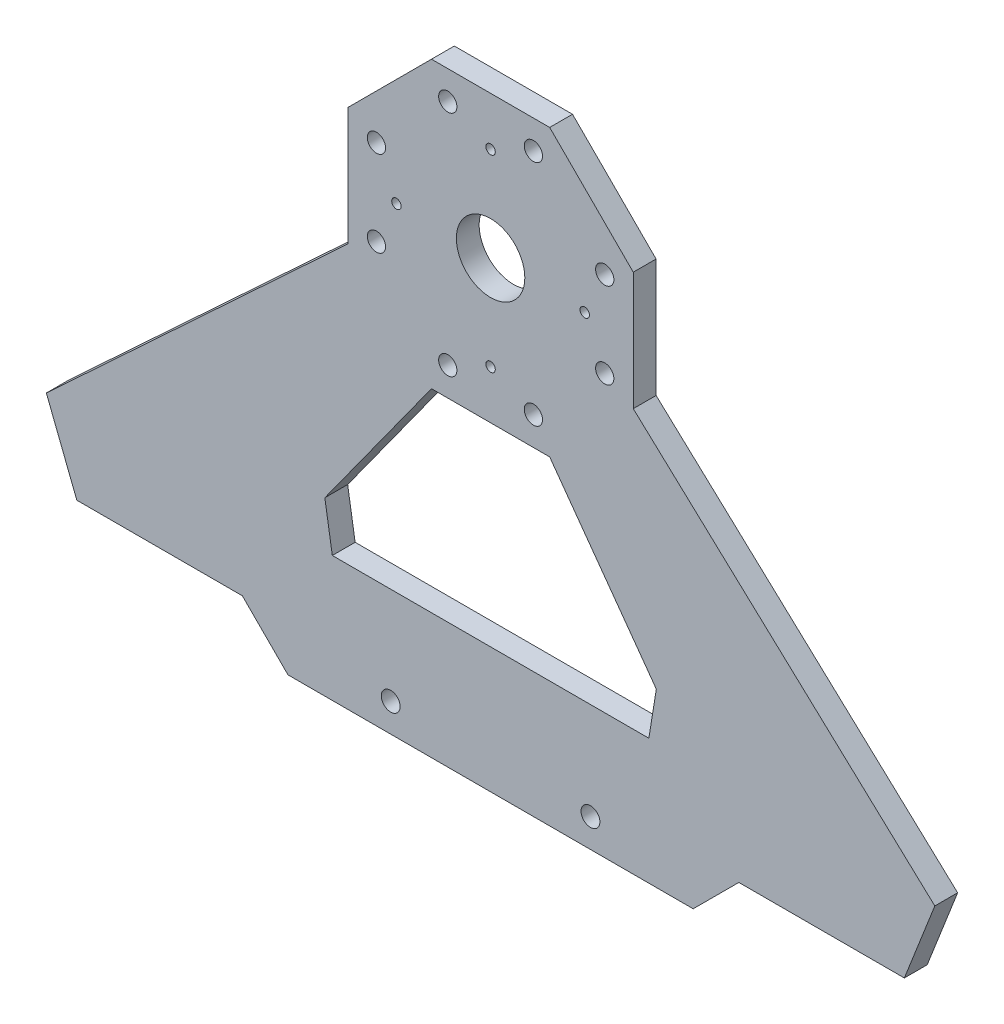
SolidWorks part; units mm, degrees
ref_plane "前视基准面" through (0, 0, 0) normal (0, 0, 1) x (1, 0, 0)
ref_plane "上视基准面" through (0, 0, 0) normal (0, 1, 0) x (1, 0, 0)
ref_plane "右视基准面" through (0, 0, 0) normal (1, 0, 0) x (0, 0, -1)
sketch "草图2" plane through (0, 0, 0) normal (0, 0, 1) x (1, 0, 0)
  line L1 (10.3553, 25) -> (-10.3553, 25)
  line L2 (-10.3553, 25) -> (-25, 10.3553)
  line L3 (-25, 10.3553) -> (-25, -10.3553)
  line L4 (-25, -10.3553) -> (-10.3553, -25)
  line L5 (-10.3553, -25) -> (10.3553, -25)
  line L6 (10.3553, -25) -> (25, -10.3553)
  line L7 (25, -10.3553) -> (25, 10.3553)
  line L8 (25, 10.3553) -> (10.3553, 25)
  circle A0 centre (0, 0) radius 25 construction
  circle A1 centre (-16.5, 0) radius 0.825
  circle A2 centre (0, 16.5) radius 0.825
  circle A3 centre (16.5, 0) radius 0.825
  circle A4 centre (0, -16.5) radius 0.825
  circle A5 centre (0, 0) radius 6
  point P22 (0, 0)
  dimension "D2" = 4
  dimension "D3" = 1.65
  dimension "D4" = 33
  dimension "D5" = 12
  dimension "D1" = 50
extrude "凸台-拉伸1" add sketch "草图2" along normal mid plane 4
sketch "草图4" plane through (0, 0, -2) normal (0, 0, -1) x (-1, 0, 0)
  line L0 (0, 2.2) -> (0, -2.2) construction
  line L1 (10.3553, -25) -> (-10.3553, -25) construction
  circle A0 centre (-7.5, -20) radius 1.6
  circle A1 centre (7.5, -20) radius 1.6
  circle A4 centre (-20, 7.5) radius 1.6
  circle A5 centre (-20, -7.5) radius 1.6
  circle A6 centre (7.5, 20) radius 1.6
  circle A7 centre (-7.5, 20) radius 1.6
  circle A8 centre (20, -7.5) radius 1.6
  circle A9 centre (20, 7.5) radius 1.6
  point P23 (0, 0)
  dimension "D1" = 15
  dimension "D2" = 5
  dimension "D3" = 3.2
  dimension "D4" = 4
extrude "切除-拉伸1" cut sketch "草图4" against normal blind 15
sketch "草图5" plane through (0, 0, 0) normal (0, 0, 1) x (1, 0, 0)
  line L0 (-25, -10.3553) -> (-92.5, -73)
  line L1 (-25, -10.3553) -> (-10.3553, -25) construction
  line L2 (-25, -10.3553) -> (-16.1777, -19.1777)
  line L3 (-16.1777, -19.1777) -> (-70, -73)
  line L4 (-70, -73) -> (-92.5, -73)
  line L5 (-10.3553, -25) -> (10.3553, -25) construction
  line L6 (0, -2.2) -> (0, 2.2) construction
  line L7 (70, -73) -> (92.5, -73)
  line L8 (16.1777, -19.1777) -> (70, -73)
  line L9 (25, -10.3553) -> (16.1777, -19.1777)
  line L10 (25, -10.3553) -> (92.5, -73)
  point P16 (0, 0)
  point P17 (-15.0357, -20.3197)
  point P18 (-92.5, -73)
  dimension "D1" = 48
  dimension "D2" = 185
  dimension "D3" = 140
extrude "凸台-拉伸2" add sketch "草图5" against normal mid plane 4
sketch "草图6" plane through (0, 0, 0) normal (0, 0, 1) x (1, 0, 0)
  line L0 (-70, -73) -> (-45, -73)
  line L9 (-45, -73) -> (-10.3553, -25)
  line L10 (-70, -73) -> (-16.1777, -19.1777)
  line L11 (-16.1777, -19.1777) -> (-10.3553, -25)
  line L12 (0, -2.2) -> (0, 2.2) construction
  line L13 (70, -73) -> (16.1777, -19.1777)
  line L14 (45, -73) -> (10.3553, -25)
  line L15 (70, -73) -> (45, -73)
  line L16 (16.1777, -19.1777) -> (10.3553, -25)
  dimension "D1" = 25
extrude "凸台-拉伸3" add sketch "草图6" along normal mid plane 4
chamfer "倒角2" distance 20 2 edges at (-92.5, -73, 0) (92.5, -73, 0)
sketch "草图8" plane through (0, 0, 0) normal (0, 0, 1) x (1, 0, 0)
  line L0 (-72.5, -73) -> (-45, -73) construction
  line L1 (-47.5, -81) -> (47.5, -81)
  line L2 (-47.5, -81) -> (-47.5, -59)
  line L3 (-47.5, -59) -> (47.5, -59)
  line L4 (47.5, -81) -> (47.5, -59)
  line L5 (-47.5, -81) -> (47.5, -59) construction
  line L6 (-47.5, -59) -> (47.5, -81) construction
  point P0 (0, -70)
  dimension "D1" = 70
  dimension "D2" = 8
  dimension "D3" = 95
extrude "凸台-拉伸4" add sketch "草图8" along normal mid plane 4
chamfer "倒角3" distance 12 angle 45 2 edges at (47.5, -81, 0) (-47.5, -81, 0)
chamfer "倒角4" distance 10 angle 45 2 edges at (34.8953, -59, 0) (-34.8953, -59, 0)
sketch "草图10" plane through (0, 0, 2) normal (0, 0, 1) x (1, 0, 0)
  line L0 (0, -2.2) -> (0, 2.2) construction
  line L1 (-35.5, -81) -> (35.5, -81) construction
  circle A0 centre (-17.5, -76) radius 1.65
  circle A1 centre (17.5, -76) radius 1.65
  dimension "D1" = 5
  dimension "D2" = 35
  dimension "D3" = 3.3
extrude "切除-拉伸2" cut sketch "草图10" against normal blind 14
